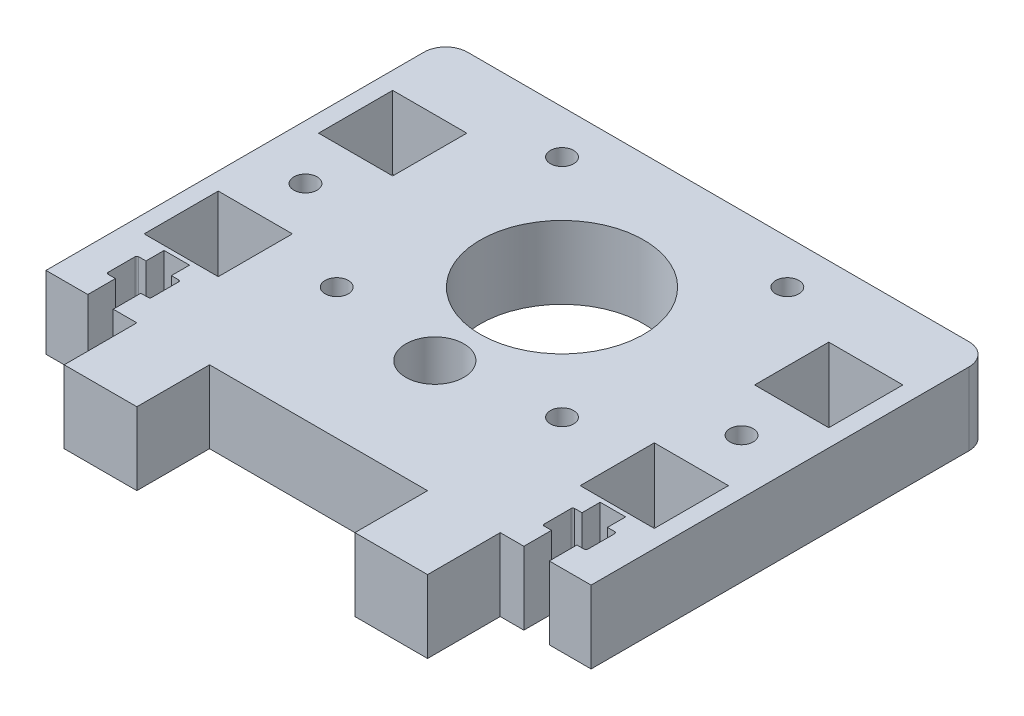
SolidWorks part; units mm, degrees
ref_plane "Front Plane" through (0, 0, 0) normal (0, 0, 1) x (1, 0, 0)
ref_plane "Top Plane" through (0, 0, 0) normal (0, 1, 0) x (1, 0, 0)
ref_plane "Right Plane" through (0, 0, 0) normal (1, 0, 0) x (0, 0, -1)
sketch "Sketch1" plane through (0, 0, 0) normal (0, 1, 0) x (1, 0, 0)
  line L0 (0, 29) -> (0, -6) construction
  line L1 (-34.5, 29) -> (0, 29)
  line L2 (-37.5, 26) -> (-37.5, -26)
  line L3 (-37.5, -26) -> (-25, -26)
  line L4 (0, 29) -> (0, 18.75)
  line L5 (0, -3.75) -> (0, -6)
  line L6 (0, -14) -> (0, -26) construction
  line L7 (-11.25, 7.5) -> (0, 7.5) construction
  line L8 (0, -14) -> (0, -26)
  line L9 (-30, 19.3) -> (-30, 9.1) construction
  line L10 (-37.5, 2.2) -> (0, 2.2) construction
  line L11 (-35.1, 19.3) -> (-24.9, 19.3)
  line L12 (-35.1, 19.3) -> (-35.1, 9.1)
  line L13 (-35.1, 9.1) -> (-24.9, 9.1)
  line L14 (-24.9, 19.3) -> (-24.9, 9.1)
  line L15 (-35.1, 19.3) -> (-24.9, 9.1) construction
  line L16 (-35.1, 9.1) -> (-24.9, 19.3) construction
  line L17 (-35.1, -4.7) -> (-24.9, -14.9) construction
  line L18 (-35.1, -14.9) -> (-24.9, -4.7) construction
  line L19 (-24.9, -14.9) -> (-24.9, -4.7)
  line L20 (-35.1, -4.7) -> (-24.9, -4.7)
  line L21 (-35.1, -14.9) -> (-35.1, -4.7)
  line L22 (-35.1, -14.9) -> (-24.9, -14.9)
  line L23 (-30, -4.7) -> (-30, -14.9) construction
  line L24 (-30, -9.8) -> (-30, 14.2) construction
  line L25 (0, 7.5) -> (-15.5, 23) construction
  line L35 (-15, -26) -> (0, -26)
  line L43 (-20, -36) -> (-20, -26.9) construction
  line L44 (-15, -26) -> (-15, -36)
  line L45 (-15, -36) -> (-25, -36)
  line L46 (-25, -36) -> (-25, -26)
  arc A1 (-34.5, 29) -> (-37.5, 26) centre (-34.5, 26) ccw
  arc A2 (0, 18.75) -> (0, -3.75) centre (0, 7.5) ccw
  circle A4 centre (-15.5, 23) radius 1.6
  circle A6 centre (-15.5, -8) radius 1.6
  circle A7 centre (-30, 2.2) radius 1.6
  arc A10 (0, -6) -> (0, -14) centre (0, -10) ccw
  point P0 (0, 0)
  point P28 (-30, 14.2)
  point P39 (-30, -9.8)
  dimension "D7" = 22.5
  dimension "D17" = 8
  dimension "D14" = 3.2
  dimension "D6" = 3
  dimension "D19" = 3.2
  dimension "D1" = 55
  dimension "D9" = 10.2
  dimension "D10" = 10.2
  dimension "D22" = 10
  dimension "D23" = 10
  dimension "D16" = 17.5
  dimension "D11" = 24
  dimension "D13" = 2.2
  dimension "D3" = 37.5
  dimension "D4" = 31
  dimension "D5" = 15.5
  dimension "D15" = 26
  dimension "D18" = 37.5
  dimension "D20" = 20
  dimension "D8" = 16
  dimension "D12" = 30
extrude "MainLayout" add sketch "Sketch1" along normal blind 10
sketch "Sketch2" plane through (0, 10, 0) normal (0, 1, 0) x (1, 0, 0)
  line L0 (-30, -26) -> (-30, -15.5) construction
  line L1 (-28.25, -22.2) -> (-28.25, -26)
  line L2 (-37.5, -26) -> (-25, -26) construction
  line L3 (-28.25, -15.5) -> (-31.75, -15.5)
  line L4 (-31.75, -15.5) -> (-31.75, -18)
  line L5 (-31.75, -18) -> (-32.75, -18)
  line L6 (-33, -18.25) -> (-33, -21.95)
  line L7 (-32.75, -22.2) -> (-31.75, -22.2)
  line L8 (-31.75, -22.2) -> (-31.75, -26)
  line L9 (-31.75, -26) -> (-28.25, -26)
  line L10 (-27.25, -22.2) -> (-28.25, -22.2)
  line L11 (-27, -18.25) -> (-27, -21.95)
  line L12 (-28.25, -18) -> (-27.25, -18)
  line L13 (-28.25, -15.5) -> (-28.25, -18)
  line L14 (0, -26) -> (0, -14) construction
  line L30 (-30, -26) -> (-30, -15.5) construction
  arc A0 (-27, -18.25) -> (-27.25, -18) centre (-27.25, -18.25) ccw
  arc A1 (-32.75, -18) -> (-33, -18.25) centre (-32.75, -18.25) ccw
  arc A2 (-27.25, -22.2) -> (-27, -21.95) centre (-27.25, -21.95) ccw
  arc A3 (-33, -21.95) -> (-32.75, -22.2) centre (-32.75, -21.95) ccw
  point P17 (0, -20)
  point P38 (-27, -18)
  point P41 (-33, -18)
  point P44 (-27, -22.2)
  point P47 (-33, -22.2)
  dimension "D8" = 0.25
  dimension "D1" = 1.75
  dimension "D2" = 0
  dimension "D3" = 4.2
  dimension "D5" = 10.5
  dimension "D6" = 3
  dimension "D4" = 8
  dimension "D7" = 30
extrude "TSlot" cut sketch "Sketch2" against normal through all
mirror "Mirror1" about plane through (0, 0, 0) normal (1, 0, 0) of "TSlot", "MainLayout"
equation "\"Y-ROD-SPACING\"=75"
equation "\"Y-BED-OFFSET\"=2"
equation "\"Y-BED-ROD-INSET\"=3.5"
equation "\"T-SLOT-NUT-FILLET-RADIUS\"=0.25"
equation "\"T-SLOT-SCREW-SHAFT-RADIUS\"=1.75"
equation "\"T-SLOT-SCREW-SHAFT-CUTOUT-LENGTH\"=10.5"
equation "\"T-SLOT-NUT-DEPTH\"=4.2"
equation "\"T-SLOT-NUT-WIDTH\"=3"
equation "\"T-SLOT-NUT-END-DISTANCE\"=8"
equation "\"ACRYLIC-TAB-CUTOUT-SIZE\"=\"ACRYLIC-THICKNESS\"+\"ACRYLIC-TAB-TOLERANCE\"*2"
equation "\"ACRYLIC-TAB-WIDTH\"=\"ACRYLIC-THICKNESS\""
equation "\"ACRYLIC-M3-HOLE\"=3.2"
equation "\"SMOOTHROD-CAP-SCREW-DISTANCE\"=20"
equation "\"FRAME-WIDTH-INNER\"=370"
equation "\"NEMA17-HOLE-SPACING\"=31"
equation "\"NEMA17-CENTRAL-CUTOUT\"=22.5"
equation "\"D7@Sketch1\"=\"NEMA17-CENTRAL-CUTOUT\""
equation "\"D5@Sketch1\"=\"NEMA17-HOLE-SPACING\"/2"
equation "\"D4@Sketch1\"=\"NEMA17-HOLE-SPACING\""
equation "\"D19@Sketch1\"=\"ACRYLIC-M3-HOLE\""
equation "\"D14@Sketch1\"=\"ACRYLIC-M3-HOLE\""
equation "\"D9@Sketch1\"=\"ACRYLIC-TAB-CUTOUT-SIZE\""
equation "\"D10@Sketch1\"=\"ACRYLIC-TAB-CUTOUT-SIZE\""
equation "\"D23@Sketch1\"=\"ACRYLIC-TAB-WIDTH\""
equation "\"D22@Sketch1\"=\"ACRYLIC-TAB-WIDTH\""
equation "\"D5@Sketch2\"=\"T-SLOT-SCREW-SHAFT-CUTOUT-LENGTH\""
equation "\"D4@Sketch2\"=\"T-SLOT-NUT-END-DISTANCE\""
equation "\"D3@Sketch2\"=\"T-SLOT-NUT-DEPTH\""
equation "\"D1@Sketch2\"=\"T-SLOT-SCREW-SHAFT-RADIUS\""
equation "\"D8@Sketch2\"=\"T-SLOT-NUT-FILLET-RADIUS\""
equation "\"Z-BRACKET-REACH\"=55"
equation "\"D1@Sketch1\"=\"Z-BRACKET-REACH\""
equation "\"Z-ROD-SPACING\"=17.5"
equation "\"ACRYLIC-THICKNESS\"=10"
equation "\"TOP-BRACKET-SPACING\"=40"
equation "\"SMOOTHROD-X-LENGTH\"=350"
equation "\"SMOOTHROD-Y-LENGTH\"=350"
equation "\"SMOOTHROD-Z-LENGTH\"=350"
equation "\"SMOOTHROD-TIGHTENING-HEADROOM\"=1"
equation "\"LEADSCREW-Z-LENGTH\"=300"
equation "\"D16@Sketch1\"=\"Z-ROD-SPACING\""
equation "\"X-ROD-SPACING\"=45"
equation "\"ACRYLIC-THICKNESS2\"=4.5"
equation "\"SCREW-LENGTH-FRAME\"=\"ACRYLIC-THICKNESS\" + 10"
equation "\"SCREW-HEAD-RADIUS\"=6"
equation "\"PRINTED-X-SMOOTHROD-DIAMETER\"=8.2"
equation "\"PRINTED-X-SMOOTHROD-CUTOUT\"=10"
equation "\"PRINTED-X-BASE-HEIGHT\"=10"
equation "\"PRINTED-LM8UU-CUTOUT-SIZE\"=15.25"
equation "\"PRINTED-LM8UU-CUTOUT-LENGTH\"=24.5"
equation "\"PRINTED-X-IDLER-HEIGHT\"=16"
equation "\"PSU-MOUNTING-WIDTH\"=95"
equation "\"PSU-MOUNTING-HEIGHT\"=177"
equation "\"D1@MainLayout\"=\"ACRYLIC-THICKNESS\""
equation "\"Z-ROD-INSET\"=16"
equation "\"Y-BELT-TO-ROD-DISTANCE\"=20"
equation "\"SPOOL-HOLDER-ROD-SPACING\"=150"
equation "\"D8@Sketch1\"=\"Z-ROD-INSET\""
equation "\"Y-BED-SCREW-SPACING\"=209"
equation "\"Y-BED-SCREW-CUTOUT-SLOT-HEIGHT\"=1"
equation "\"ACRYLIC-TAB-TOLERANCE\"=.1"
equation "\"SCREW-LENGTH-MOTOR\"=\"ACRYLIC-THICKNESS\" + 5"
equation "\"SCREW-LENGTH-EXTRUDER\"=28"
equation "\"ACRYLIC-X-CARRIAGE-WIDTH\"=55"
equation "\"ACRYLIC-X-CARRIAGE-HEIGHT\"=75"
equation "\"ACRYLIC-X-CARRIAGE-LM8UU-CUTOUT-WIDTH\"=24.25"
equation "\"ACRYLIC-X-CARRIAGE-SCREW-SPACING-X\"=15"
equation "\"ACRYLIC-X-CARRIAGE-SCREW-SPACING-Y\"=33"
equation "\"ACRYLIC-X-CARRIAGE-CENTER-TAB-SPACING\"=14"
equation "\"ACRYLIC-X-CARRIAGE-EXTRUDER-OFFSET\"=26"
equation "\"ACRYLIC-X-CARRIAGE-EXTRUDER-ANGLE\"=90"
equation "\"ACRYLIC-X-CARRIAGE-EXTRUDER-SHELF-DEPTH\"=\"ACRYLIC-X-CARRIAGE-EXTRUDER-OFFSET\" + 30"
equation "\"ACRYLIC-X-CARRIAGE-EXTRUDER-BRACE-SPACING\"=23"
equation "\"ACRYLIC-X-CARRIAGE-EXTRUDER-BRACE-TAB-OFFSET\"=20"
equation "\"ACRYLIC-X-CARRIAGE-EXTRUDER-BRACE-HEIGHT\"=35"
equation "\"ACRYLIC-X-CARRIAGE-EXTRUDER-BRACE-SCREW-SPACING\"=22"
